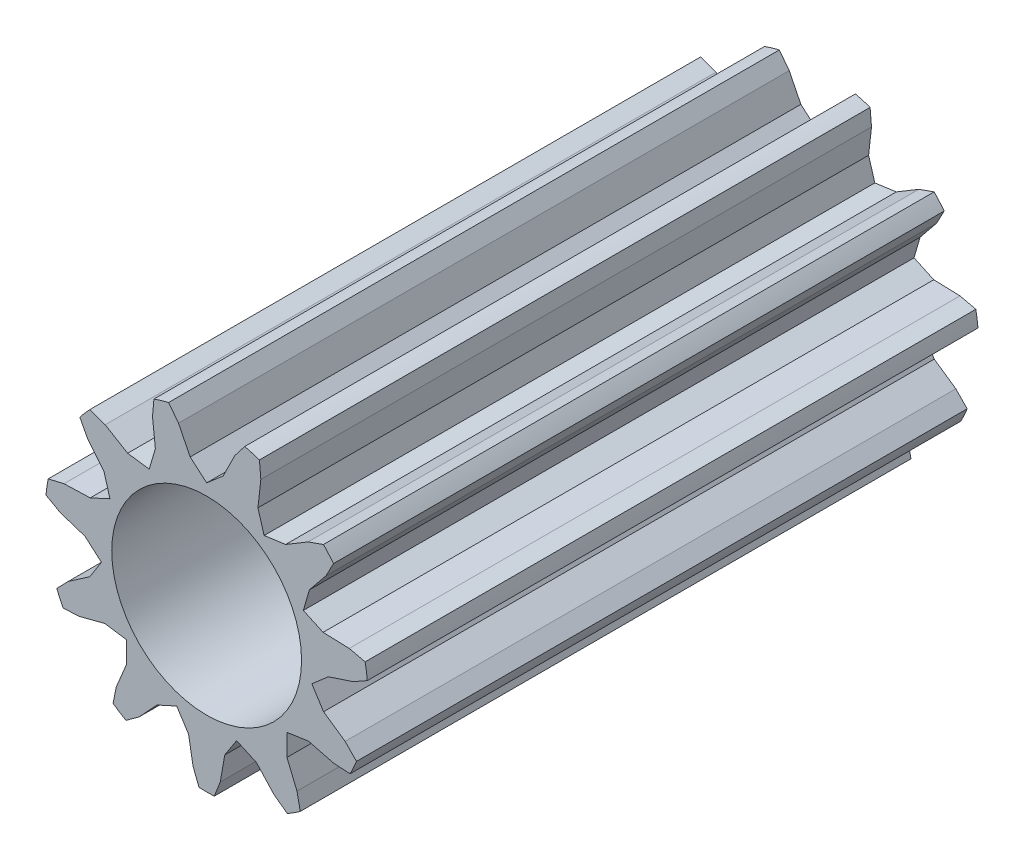
SolidWorks part; units mm, degrees
ref_plane "Front Plane" through (0, 0, 0) normal (0, 0, 1) x (1, 0, 0)
ref_plane "Top Plane" through (0, 0, 0) normal (0, 1, 0) x (1, 0, 0)
ref_plane "Right Plane" through (0, 0, 0) normal (1, 0, 0) x (0, 0, -1)
sketch "Sketch1" plane through (0, 0, 0) normal (0, 0, 1) x (1, 0, 0)
  line L1 (4.0659, -4.0659) -> (-4.0659, -4.0659) construction
  line L2 (4.0659, -4.0659) -> (4.0659, 4.0659) construction
  line L3 (4.0659, 4.0659) -> (-4.0659, 4.0659) construction
  line L4 (-4.0659, -4.0659) -> (-4.0659, 4.0659) construction
  line L5 (4.0659, -4.0659) -> (-4.0659, 4.0659) construction
  line L6 (4.0659, 4.0659) -> (-4.0659, -4.0659) construction
  circle A0 centre (0, 0) radius 9.7778
  circle A1 centre (0, 0) radius 5.75 construction
  dimension "D1" = 19.5556
  dimension "D2" = 11.5
extrude "Boss-Extrude1" add sketch "Sketch1" along normal blind 37
sketch "Sketch2" plane through (0, 0, 0) normal (0, 0, 1) x (1, 0, 0)
  line L0 (0, 0) -> (0, 10.088) construction
  line L1 (0, 6.4402) -> (-0.9985, 7.2997)
  line L8 (-1.7043, 10.285) -> (0, 10.9993)
  line L11 (-0.9985, 7.2997) -> (-1.7043, 8.7207)
  line L12 (-1.7043, 8.7207) -> (-2.3066, 9.5018)
  line L13 (-2.3066, 9.5018) -> (-1.7043, 10.285)
  line L14 (2.3066, 9.5018) -> (1.7043, 10.285)
  line L15 (1.7043, 8.7207) -> (2.3066, 9.5018)
  line L16 (0.9985, 7.2997) -> (1.7043, 8.7207)
  line L17 (1.7043, 10.285) -> (0, 10.9993)
  line L18 (0, 6.4402) -> (0.9985, 7.2997)
  circle A14 centre (0, 0) radius 9.7778 construction
  point P16 (0, 9.7778)
  dimension "D5" = 0.6023
  dimension "D6" = 0.7811
  dimension "D1" = 0.9985
  dimension "D2" = 0.8594
  dimension "D3" = 0.7058
  dimension "D4" = 1.4211
  dimension "D7" = 0.7832
  dimension "D8" = 0.6023
  dimension "D9" = 0.7142
  dimension "D10" = 1.7043
extrude "Cut-Extrude1" cut sketch "Sketch2" along normal through all
sketch "Sketch3" plane through (0, 0, 0) normal (0, 0, 1) x (1, 0, 0)
  circle A0 centre (0, 0) radius 7.5
  dimension "D1" = 15
sketch "Sketch4" plane through (0, 0, 37) normal (0, 0, 1) x (1, 0, 0)
  circle A0 centre (0, 0) radius 5.75
  dimension "D1" = 11.5
extrude "Cut-Extrude2" cut sketch "Sketch4" against normal through all both and the other way through all
pattern_circular "CirPattern1" count 11 over 360 about axis through (0, 0, 37) along (0, 0, -1) of "Cut-Extrude1" reverse direction yes
sketch "Sketch5" plane through (0, 0, 0) normal (0, 0, 1) x (1, 0, 0)
  line L0 (0, 0) -> (0, 16.5734) construction
  arc A0 (0, 2.7703) -> (-2.7395, 5.5802) centre (3.9333, 9.3453) cw
  arc A1 (-2.7395, 5.5802) -> (0, 7.0858) centre (3.4783, -2.4876) cw
  arc A2 (2.7395, 5.5802) -> (0, 7.0858) centre (-3.4783, -2.4876) ccw
  arc A3 (0, 2.7703) -> (2.7395, 5.5802) centre (-3.9333, 9.3453) ccw
sketch "Sketch8" plane through (0, 0, 37) normal (0, 0, 1) x (1, 0, 0)
  line L0 (0, 5.75) -> (0, -5.75) construction
  line L1 (-5.75, 0) -> (5.75, 0) construction
  circle A0 centre (0, 0) radius 5.75 construction
equation "\"circle\"=19.5556"
equation "\"D1@Sketch1\"=\"circle\""
equation "\"separator_width\"=45"
equation "\"big-gear-thiccness\"=2"
equation "\"D1@Boss-Extrude1\"=\"separator_width\" - \"big-gear-thiccness\"-10/2+2-3"
